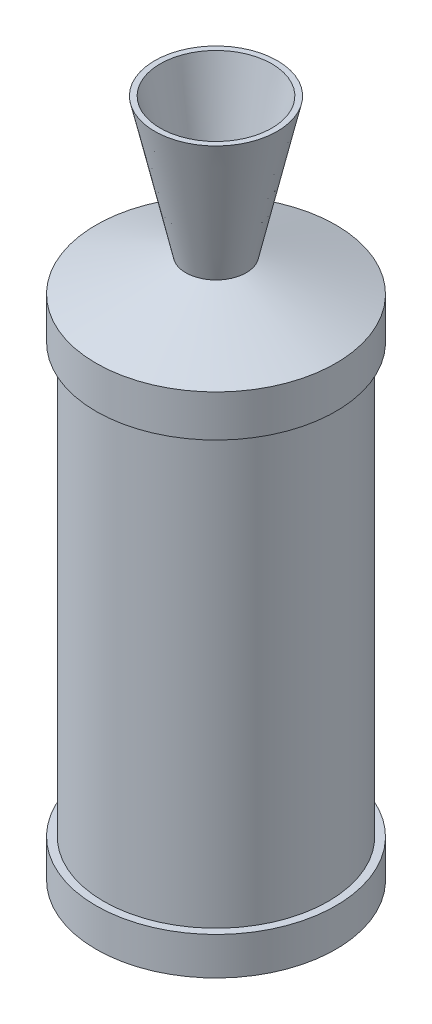
SolidWorks part; units mm, degrees
material "TLCorrectionEngine"
ref_plane "Front Plane" through (0, 0, 0) normal (0, 0, 1) x (1, 0, 0)
ref_plane "Top Plane" through (0, 0, 0) normal (0, 1, 0) x (1, 0, 0)
ref_plane "Right Plane" through (0, 0, 0) normal (1, 0, 0) x (0, 0, -1)
sketch "Sketch1" plane through (0, 0, 0) normal (0, 0, 1) x (1, 0, 0)
  line L0 (0, 0) -> (279.4, 0) construction
  line L1 (102.37, 0) -> (102.37, 514.35) construction
  line L2 (102.37, 34.44) -> (434.7994, 34.44) construction
  line L3 (109.297, 34.44) -> (109.297, 895.35) construction
  line L4 (109.297, 68.84) -> (-39.6106, 68.84) construction
  line L5 (102.37, 459.22) -> (711.3913, 459.22) construction
  line L6 (109.297, 497.22) -> (-188.2082, 497.22) construction
  line L7 (0, 0) -> (0, 876.3) construction
  line L8 (0, 527.83) -> (410.1256, 527.83) construction
  line L9 (0, 653.67) -> (316.3906, 653.67) construction
  line L10 (0, 0) -> (19, 0)
  line L11 (19, 0) -> (102.37, 34.44)
  line L12 (102.37, 34.44) -> (109.297, 34.44)
  line L13 (109.297, 34.44) -> (109.297, 68.84)
  line L14 (109.297, 68.84) -> (102.37, 68.84)
  line L15 (102.37, 68.84) -> (102.37, 459.22)
  line L16 (102.37, 459.22) -> (109.297, 459.22)
  line L17 (109.297, 459.22) -> (109.297, 497.22)
  line L18 (109.297, 497.22) -> (27.555, 527.83)
  line L19 (27.555, 527.83) -> (55.87, 653.67)
  line L20 (0, 4) -> (82.2452, 4) construction
  line L21 (19, 0) -> (19, 38.1) construction
  line L22 (102.37, 34.44) -> (72.8556, 34.44) construction
  line L23 (98.37, 34.44) -> (98.37, 813.7021) construction
  line L24 (0, 0) -> (0, 4)
  line L25 (0, 4) -> (19, 4)
  line L26 (19, 4) -> (98.37, 34.44)
  line L27 (98.37, 34.44) -> (98.37, 497.22)
  line L28 (31.1633, 527.83) -> (-71.6827, 650.3971) construction
  line L29 (31.1633, 527.83) -> (69.85, 425.45) construction
  line L30 (-7.404, 573.7927) -> (35.714, 564.0908) construction
  line L31 (52.372, 471.7035) -> (68.426, 512.525) construction
  line L32 (31.6204, 565.0119) -> (50.87, 653.67)
  line L33 (50.87, 653.67) -> (55.87, 653.67)
  line L34 (67.0115, 508.9283) -> (98.37, 497.22)
  line L35 (6.35, 12.7) -> (95.357, 42.6531)
  line L36 (95.357, 491.6004) -> (6.35, 508)
  line L37 (95.357, 42.6531) -> (95.357, 491.6004)
  line L38 (6.35, 508) -> (6.35, 12.7)
  circle A0 centre (31.1633, 527.83) radius 20 construction
  circle A1 centre (-7.404, 573.7927) radius 40 construction
  circle A2 centre (52.372, 471.7035) radius 40 construction
  arc A3 (38.2329, 509.1212) -> (18.3075, 543.1509) centre (31.1633, 527.83) cw
  arc A4 (18.3075, 543.1509) -> (31.6204, 565.0119) centre (-7.404, 573.7927) ccw
  arc A5 (38.2329, 509.1212) -> (67.0115, 508.9283) centre (52.372, 471.7035) cw
  point P0 (0, 0)
  point P4 (102.37, 0)
  point P7 (102.37, 34.44)
  point P8 (19, 0)
  point P11 (109.297, 34.44)
  point P14 (109.297, 68.84)
  point P17 (102.37, 68.84)
  point P18 (102.37, 459.22)
  point P21 (109.297, 459.22)
  point P22 (109.297, 497.22)
  point P25 (0, 497.22)
  point P27 (0, 527.83)
  point P30 (27.555, 527.83)
  point P31 (11.1633, 527.83)
  point P32 (0, 653.67)
  point P35 (55.87, 653.67)
  point P36 (0, 4)
  point P44 (19, 4)
  point P46 (98.37, 34.44)
  point P50 (31.1633, 527.83)
  point P55 (52.372, 471.7035)
  point P58 (-7.404, 573.7927)
  point P69 (50.87, 653.67)
  point P70 (6.35, 12.7)
  point P73 (6.35, 508)
  dimension "D1" = 102.37
  dimension "D2" = 34.44
  dimension "D3" = 19
  dimension "D4" = 6.927
  dimension "D5" = 34.4
  dimension "D6" = 390.38
  dimension "D7" = 38
  dimension "D8" = 30.61
  dimension "D9" = 27.555
  dimension "D10" = 11.1633
  dimension "D11" = 125.84
  dimension "D12" = 55.87
  dimension "D13" = 4
  dimension "WHALL_C" = 4
  dimension "D14" = 60
  dimension "R_INTERNAL" = 20
  dimension "D15" = 60
  dimension "D16" = 5
revolve "Revolve1" add sketch "Sketch1" angle 360 about L7
equation "\"D13@Sketch1\" = \"WHALL_C\""
equation "\"D14@Sketch1\" = \"R_INTERNAL\"*3"
equation "\"D15@Sketch1\" = \"R_INTERNAL\"*3"
